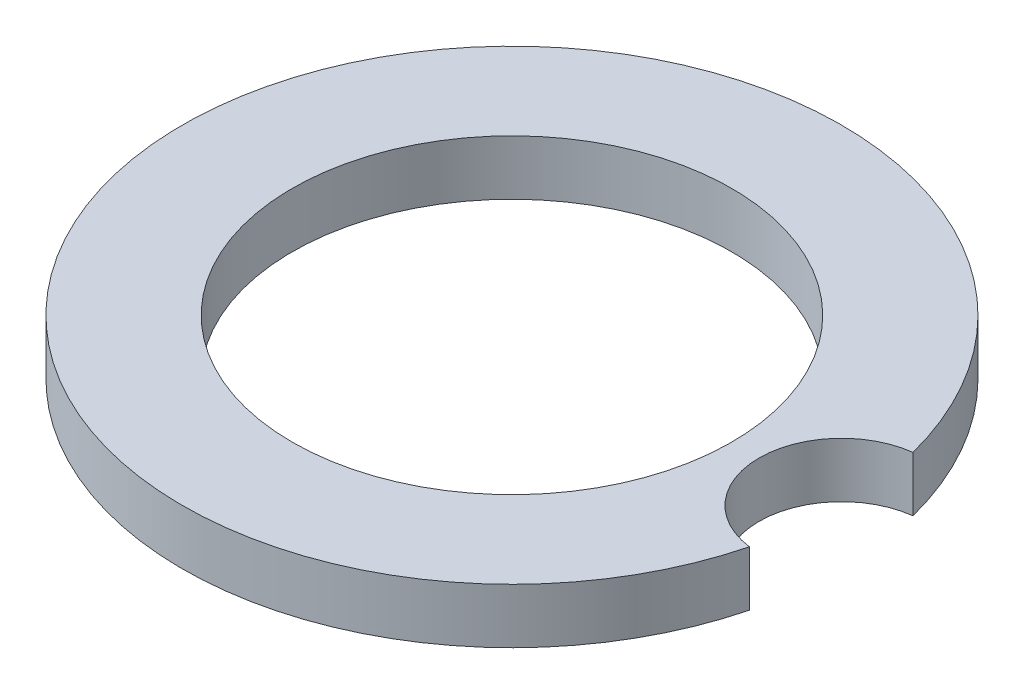
SolidWorks part; units mm, degrees
ref_plane "Front Plane" through (0, 0, 0) normal (0, 0, 1) x (1, 0, 0)
ref_plane "Top Plane" through (0, 0, 0) normal (0, 1, 0) x (1, 0, 0)
ref_plane "Right Plane" through (0, 0, 0) normal (1, 0, 0) x (0, 0, -1)
sketch "Sketch1" plane through (0, 0, 0) normal (0, 1, 0) x (1, 0, 0)
  circle A0 centre (0, 0) radius 50.8
  circle A1 centre (0, 0) radius 76.1746
  dimension "Front_CR_ID" = 101.6
  dimension "Front_CR_OD" = 152.3492
extrude "Boss-Extrude1" add sketch "Sketch1" along normal blind 12.7 contours A1
extrude "Cut-Extrude2" cut sketch "Sketch1<10>" along normal through all contours A0
sketch "Sketch1<10>" plane through (0, 0, 0) normal (0, 1, 0) x (1, 0, 0) same geometry as "Sketch1"
sketch "Sketch2" plane through (0, 12.7, 0) normal (0, 1, 0) x (1, 0, 0)
  line L0 (76.2, 19.05) -> (76.2, -19.05)
  arc A0 (76.2, 19.05) -> (76.2, -19.05) centre (76.1746, 0) ccw
  circle A1 centre (0, 0) radius 76.1746 construction
  dimension "D1" = 38.1
extrude "Cut-Extrude3" cut sketch "Sketch2" against normal through all contours A0 L0
ref_plane "Plane1" through (0, 6.35, 0) normal (0, -1, 0) x (-1, 0, 0)
equation "\"Bodytube_OD\" = 6.17in"
equation "\"Bodytube_ID\" = 5.998in"
equation "\"Motor_OD\" = 4in"
equation "\"Fwd_Tube_Length\" = 40in"
equation "\"Mid_Tube_Length\" = 1in"
equation "\"Aft_Section_Length\"= 39in"
equation "\"Mid_Coupler_Length\" = 13in"
equation "\"Aft_Lower_Length\"= 22in"
equation "\"AB_Coupler_OD_Length\"= 1in"
equation "\"AB_Coupling_Section_Length\"= 0.375in"
equation "\"AB_Coupler_Length\"= \"AB_Coupler_OD_Length\" + \"AB_Coupling_Section_Length\" * 2"
equation "\"Cutout_Angle\" = 80"
equation "\"AB_Paddle_Height\" = 0.375in"
equation "\"AB_Coupler_Num_Screws\"= 6"
equation "\"Num_Cutouts\" = 3"
equation "\"AB_Coupler_OD\"= 6.17in"
equation "\"AB_Coupler_ID\"= 5.75in"
equation "\"AB_Coupler_Surface_Diameter\"= 5.998in"
equation "\"AB_Coupling_Screw_Diameter\"= 0.1065in"
equation "\"AB_Central_Bushing_Length\" = .75in"
equation "\"Lead_Screw_Dist\" = 2.25in"
equation "\"Lead_Screw_Diam\" = 11mm"
equation "\"Lead_Screw_Length\" = (\"Mid_Coupler_Length\" + 2*0.375in + 2*0.5in)"
equation "\"Paddle_Pin_Offset\" = .25in"
equation "\"Paddle_Pin_Radius\" = 2.25in"
equation "\"Paddle_Gear_OD\" = 3.2in"
equation "\"Fwd_BKHD_From_Top\" = 18in"
equation "\"Front_CR_OD@Sketch1\"=\"Bodytube_ID\""
equation "\"Front_CR_ID@Sketch1\"=\"Motor_OD\""
